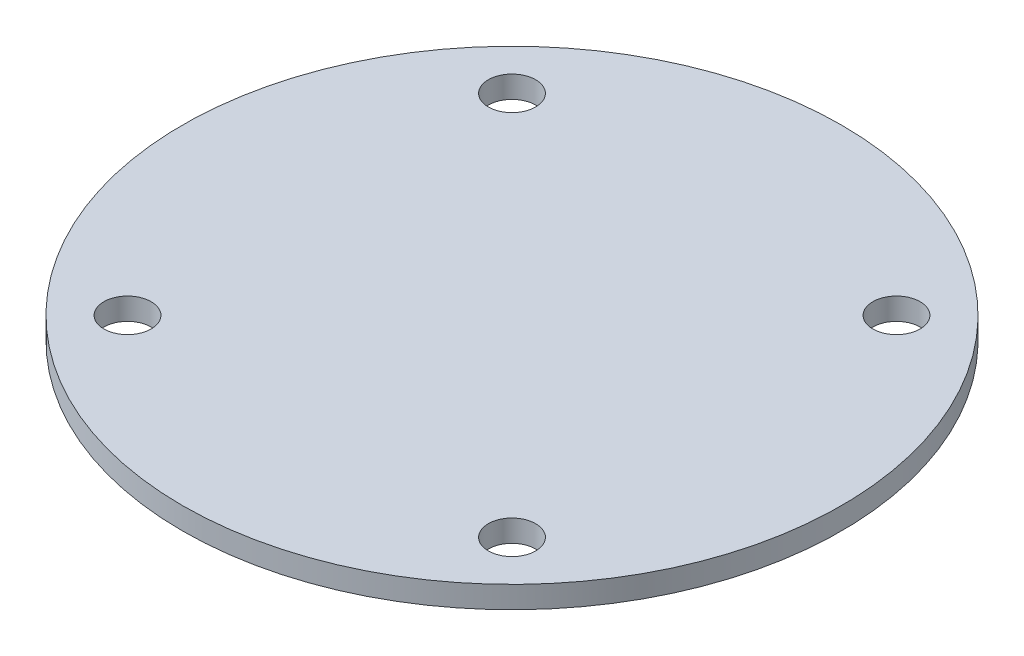
SolidWorks part; units mm, degrees
material "Epoxy, Unfilled"
ref_plane "Front Plane" through (0, 0, 0) normal (0, 0, 1) x (1, 0, 0)
ref_plane "Top Plane" through (0, 0, 0) normal (0, 1, 0) x (1, 0, 0)
ref_plane "Right Plane" through (0, 0, 0) normal (1, 0, 0) x (0, 0, -1)
ref_axis "x-axis" through (88.99, 0, 0) along (-1, 0, 0)
ref_axis "y-axis" through (0, 0, 55) along (0, 0, -1)
ref_axis "z-axis" through (0, 55, 0) along (0, -1, 0)
sketch "Sketch2" plane through (0, 0, 0) normal (0, 1, 0) x (1, 0, 0)
  circle A0 centre (0, 0) radius 30
  dimension "D1" = 60
extrude "AcrylicBase" add sketch "Sketch2" against normal blind 2
hole_wizard "#8 Clearance Hole2" positions "Sketch8" profile "Sketch7" hole size "#8" standard "Ansi Inch" end condition through all
sketch "Sketch8" plane through (0, 0, 0) normal (0, 1, 0) x (-1, 0, 0)
  line L0 (17.5, -17.5) -> (-17.5, -17.5) construction
  line L1 (-17.5, -17.5) -> (-17.5, 17.5) construction
  line L2 (-17.5, 17.5) -> (17.5, 17.5) construction
  line L3 (17.5, 17.5) -> (17.5, -17.5) construction
  line L5 (17.5, 0) -> (-17.5, 0) construction
  line L7 (0, -17.5) -> (0, 17.5) construction
  point P0 (17.5, -17.5)
  point P1 (-17.5, -17.5)
  point P2 (-17.5, 17.5)
  point P4 (17.5, 17.5)
  dimension "D1" = 35
  dimension "D2" = 35
sketch "Sketch7" plane through (-17.5, 0, -17.5) normal (1, 0, 0) x (0, 0, 1)
  line L0 (0, 0) -> (0, 2)
  line L1 (0, 2) -> (2.1526, 2)
  line L2 (2.1526, 2) -> (2.1526, 0)
  line L5 (2.1526, 0) -> (0, 0)
  line L11 (0, -6.35) -> (0, 107.95) construction
  dimension "Thru Hole Dia." = 4.3053
  dimension "Thru Hole Depth" = 2
